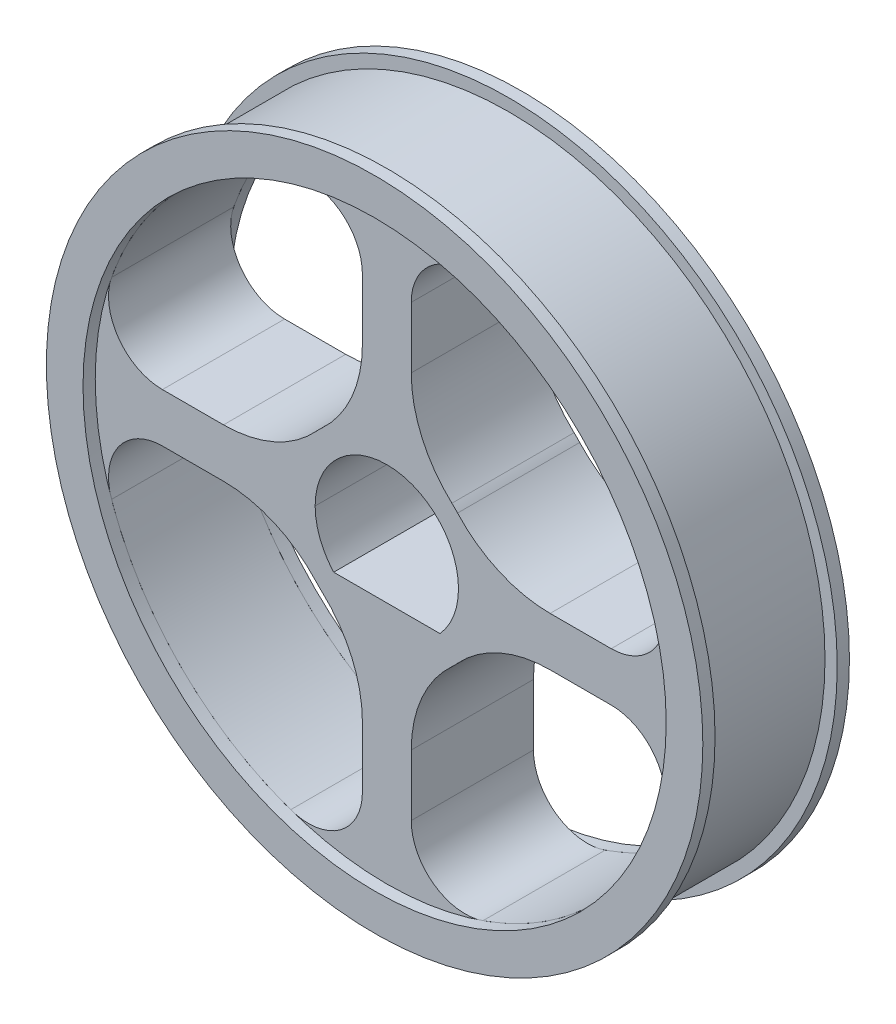
SolidWorks part; units mm, degrees
material "ABS"
ref_plane "Front Plane" through (0, 0, 0) normal (0, 0, 1) x (1, 0, 0)
ref_plane "Top Plane" through (0, 0, 0) normal (0, 1, 0) x (1, 0, 0)
ref_plane "Right Plane" through (0, 0, 0) normal (1, 0, 0) x (0, 0, -1)
sketch "Sketch1" plane through (0, 0, 0) normal (0, 0, 1) x (1, 0, 0)
  line L0 (-14.5852, 8.3594) -> (-14.5852, 12.4234) construction
  line L2 (-14.0772, 11.0264) -> (-14.0772, 9.7564)
  line L3 (-13.4806, 5.3614) -> (-15.6898, 5.3614)
  line L4 (-15.0932, 11.0264) -> (-15.0932, 9.7564)
  line L5 (-9.9202, 6.8694) -> (-11.1902, 6.8694)
  line L6 (-14.5852, 10.3914) -> (-15.0932, 10.3914) construction
  line L7 (-9.9202, 5.8534) -> (-11.1902, 5.8534)
  line L8 (-14.0772, 1.6964) -> (-14.0772, 2.9664)
  line L9 (-15.0932, 1.6964) -> (-15.0932, 2.9664)
  line L10 (-19.2502, 5.8534) -> (-17.9802, 5.8534)
  line L11 (-19.2502, 6.8694) -> (-17.9802, 6.8694)
  circle A1 centre (-14.5852, 6.3614) radius 1.998
  circle A5 centre (-14.5852, 6.3614) radius 6.062
  arc A6 (-13.0952, 6.3614) -> (-16.0752, 6.3614) centre (-14.5852, 6.3614) ccw
  circle A7 centre (-14.5852, 6.3614) radius 6.57
  circle A8 centre (-14.5852, 6.3614) radius 6.824
  arc A9 (-15.0932, 11.0264) -> (-16.5835, 12.0846) centre (-16.214, 11.0264) ccw
  arc A10 (-15.0932, 9.7564) -> (-15.9378, 7.8319) centre (-17.708, 9.7564) cw
  arc A11 (-14.0772, 9.7564) -> (-13.2326, 7.8319) centre (-11.4624, 9.7564) ccw
  arc A12 (-14.0772, 11.0264) -> (-12.5869, 12.0846) centre (-12.9564, 11.0264) cw
  arc A13 (-11.1902, 6.8694) -> (-13.1147, 7.714) centre (-11.1902, 9.4842) cw
  arc A14 (-9.9202, 6.8694) -> (-8.862, 8.3597) centre (-9.9202, 7.9902) ccw
  arc A15 (-9.9202, 5.8534) -> (-8.862, 4.3631) centre (-9.9202, 4.7326) cw
  arc A16 (-11.1902, 5.8534) -> (-13.1147, 5.0088) centre (-11.1902, 3.2386) ccw
  arc A17 (-14.0772, 2.9664) -> (-13.2326, 4.8909) centre (-11.4624, 2.9664) cw
  arc A18 (-14.0772, 1.6964) -> (-12.5869, 0.6382) centre (-12.9564, 1.6964) ccw
  arc A19 (-15.0932, 1.6964) -> (-16.5835, 0.6382) centre (-16.214, 1.6964) cw
  arc A20 (-15.0932, 2.9664) -> (-15.9378, 4.8909) centre (-17.708, 2.9664) ccw
  arc A21 (-17.9802, 5.8534) -> (-16.0557, 5.0088) centre (-17.9802, 3.2386) cw
  arc A22 (-19.2502, 5.8534) -> (-20.3083, 4.3631) centre (-19.2502, 4.7326) ccw
  arc A23 (-19.2502, 6.8694) -> (-20.3083, 8.3597) centre (-19.2502, 7.9902) cw
  arc A24 (-17.9802, 6.8694) -> (-16.0557, 7.714) centre (-17.9802, 9.4842) ccw
  spline S6 degree 3 poles (-16.0752, 6.3614) (-16.0746, 6.3309) (-16.0736, 6.27) (-16.0649, 6.179) (-16.0487, 6.0737) (-16.0209, 5.9549) (-15.9774, 5.8248) (-15.9223, 5.6991) (-15.8557, 5.5793) (-15.779, 5.4654) (-15.7195, 5.3961) (-15.6898, 5.3614) knots 0 0 0 0 0.083398 0.166639 0.250037 0.375031 0.500025 0.625018 0.750012 0.875006 1 1 1 1
  spline S7 degree 3 poles (-13.4806, 5.3614) (-13.4605, 5.3843) (-13.4205, 5.4302) (-13.3658, 5.5035) (-13.3072, 5.5925) (-13.248, 5.6992) (-13.1929, 5.8248) (-13.1494, 5.9549) (-13.1184, 6.0885) (-13.0988, 6.2244) (-13.0964, 6.3157) (-13.0952, 6.3614) knots 0 0 0 0 0.083398 0.166639 0.250037 0.375031 0.500025 0.625018 0.750012 0.875006 1 1 1 1
  point P4 (-18.4957, 7.0986)
  point P22 (0, 0)
  point P64 (-14.5852, 6.3614)
  dimension "D1" = 0.508
  dimension "D2" = 0.508
  dimension "D3" = 5.08
  dimension "D4" = 0.254
  dimension "D5" = 0.508
  dimension "D6" = 1.27
  dimension "D7" = 4
extrude "Boss-Extrude1" add sketch "Sketch1" along normal mid plane 2.54 contours A7 A5 | L2 A12 A5 A9 L4 A10 A1 A11 | A16 L7 A15 A5 A14 L5 A13 A1 | A24 L11 A23 A5 A22 L10 A21 A1 | A20 L9 A19 A5 A18 L8 A17 A1 | A1 S7 L3 S6 A6 region at (-14.5852, 10.481, 0) region at (-13.2123, 7.7342, 0) region at (-10.4656, 6.3614, 0) region at (-18.7048, 6.3614, 0) region at (-14.5852, 2.2418, 0) region at (-20.9693, 6.3614, 0)
extrude "Boss-Extrude2" add sketch "Sketch1<5>" along normal blind 0.254 from surface separate body contours A7 A5 | A8 A7 region at (-20.9693, 6.3614, 0) region at (-21.2162, 6.3614, 0) starting at face at (-12.1016, 3.8778, 1.27)
sketch "Sketch1<5>" plane through (0, 0, 0) normal (0, 0, 1) x (1, 0, 0) same geometry as "Sketch1"
mirror "Mirror2" about plane through (0, 0, 0) normal (0, 0, 1) of bodies 105 102
